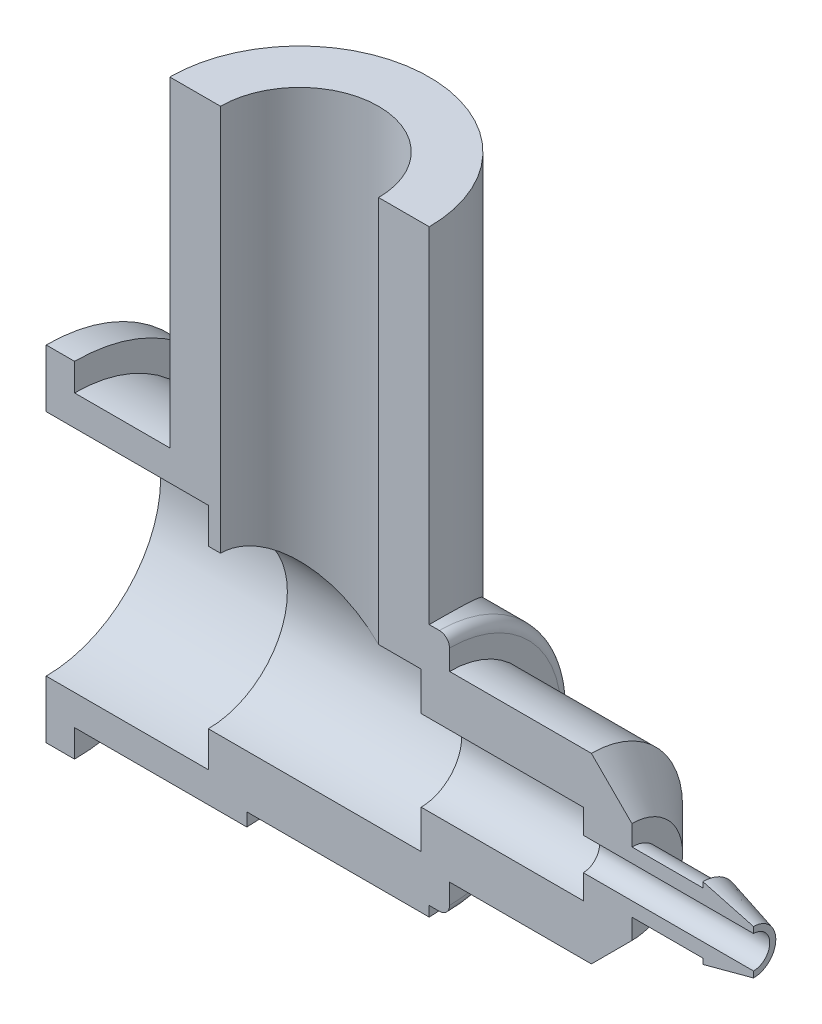
SolidWorks part; units mm, degrees
note: '?' marks a value the reader was unsure of.
ref_plane "Plan1" through (0, 0, 0) normal (0, 0, 1) x (1, 0, 0)
ref_plane "Plan2" through (0, 0, 0) normal (0, 1, 0) x (1, 0, 0)
ref_plane "Plan3" through (0, 0, 0) normal (1, 0, 0) x (0, 0, -1)
sketch "Esquisse1" plane through (0, 0, 0) normal (0, 0, 1) x (1, 0, 0)
  line L0 (0, 0) -> (0, 8.5)
  line L1 (0, 8.5) -> (1.4, 8.5)
  line L2 (1.4, 8.5) -> (1.4, 7.15)
  line L3 (9.9, 6) -> (19.9, 6)
  line L4 (19.9, 6) -> (19.9, 4.5)
  line L5 (19.9, 4.5) -> (26.9, 4.5)
  line L6 (26.9, 4.5) -> (28.9, 2.5)
  line L7 (28.9, 2.5) -> (28.9, 1.5)
  line L8 (28.9, 1.5) -> (32.4, 1.5)
  line L9 (34.9, 1.1) -> (34.9, 0)
  line L10 (0, 0) -> (34.9, 0)
  line L11 (0, 0) -> (111, 0) construction
  line L12 (32.4, 1.5) -> (32.4, 1.7699)
  line L13 (32.4, 1.7699) -> (34.9, 1.1)
  line L14 (1.4, 7.15) -> (9.9, 7.15)
  line L15 (9.9, 7.15) -> (9.9, 6)
  dimension "D1" = 17
  dimension "D2" = 14.3
  dimension "D3" = 12
  dimension "D4" = 9
  dimension "D5" = 3
  dimension "D7" = 6
  dimension "D8" = 2.5
  dimension "D10" = 2
  dimension "D11" = 7
  dimension "D12" = 10
  dimension "D13" = 8.5
  dimension "D14" = 1.4
  dimension "D21" = 2.2
  dimension "D22" = 135
revolve "Base-Révolution" add sketch "Esquisse1" angle 360 about L11
sketch "Esquisse2" plane through (0, 0, 0) normal (0, 0, 1) x (1, 0, 0)
  line L0 (12.5, 24) -> (12.5, -13) construction
  line L1 (8.6, 23) -> (8.6, -4)
  line L2 (12.5, -6.5) -> (6.1, -6.5)
  line L3 (12.5, -6.5) -> (12.5, -4)
  line L4 (8.6, 23) -> (6.1, 23)
  line L5 (6.1, -6.5) -> (6.1, 23)
  line L6 (8.6, -4) -> (12.5, -4)
  dimension "D1" = 12.5
  dimension "D2" = 12.8
  dimension "D3" = 23
  dimension "D4" = 29.5
  dimension "D5" = 7.8
  dimension "D6" = 2.5
revolve "Boss.-Révol.1" add sketch "Esquisse2" angle 360 about L0
sketch "Esquisse7" plane through (0, 0, 0) normal (0, 0, 1) x (1, 0, 0)
  line L0 (34.9, 0.8) -> (34.9, 0)
  line L1 (36, 0) -> (27, 0) construction
  line L10 (0, 5.65) -> (0, 0)
  line L16 (0, 5.65) -> (8, 5.65)
  line L17 (8, 5.65) -> (8, 3.9)
  line L18 (8, 3.9) -> (18.5, 3.9)
  line L19 (18.5, 3.9) -> (18.5, 2)
  line L20 (18.5, 2) -> (26.5, 2)
  line L21 (26.5, 2) -> (26.5, 0.8)
  line L22 (26.5, 0.8) -> (34.9, 0.8)
  line L23 (0, 0) -> (34.9, 0)
  line L24 (0, 0) -> (111, 0) construction
  dimension "D1" = 7.8
  dimension "D2" = 0.8
  dimension "D3" = 2
  dimension "D4" = 8
  dimension "D5" = 5.65
revolve "Enlèvement de matière-Révolution1" cut sketch "Esquisse7" angle 360 about L1
fillet "Congé1" radius 0.5 2 edges at (19.9, 0, 6) (9.9, 0, 7.15)
sketch "Esquisse9" plane through (0, 23, 0) normal (0, 1, 0) x (-1, 0, 0)
  circle A0 centre (-12.5, 0) radius 3.9
  circle A1 centre (-12.5, 0) radius 3.9 construction
extrude "Enlèv. mat.-Extru.4" cut sketch "Esquisse9" against normal blind 23
sketch "Esquisse10" plane through (0, 0, 0) normal (0, 0, 1) x (1, 0, 0)
  line L1 (-3.184, 26.5814) -> (36.4262, 26.5814)
  line L2 (-3.184, 26.5814) -> (-3.184, -12.3182)
  line L3 (-3.184, -12.3182) -> (36.4262, -12.3182)
  line L4 (36.4262, 26.5814) -> (36.4262, -12.3182)
extrude "Enlèv. mat.-Extru.5" cut sketch "Esquisse10" along normal through all
ref_axis "Axe1" through (12.5, -4.3772, 0) along (0, 1, 0)?
